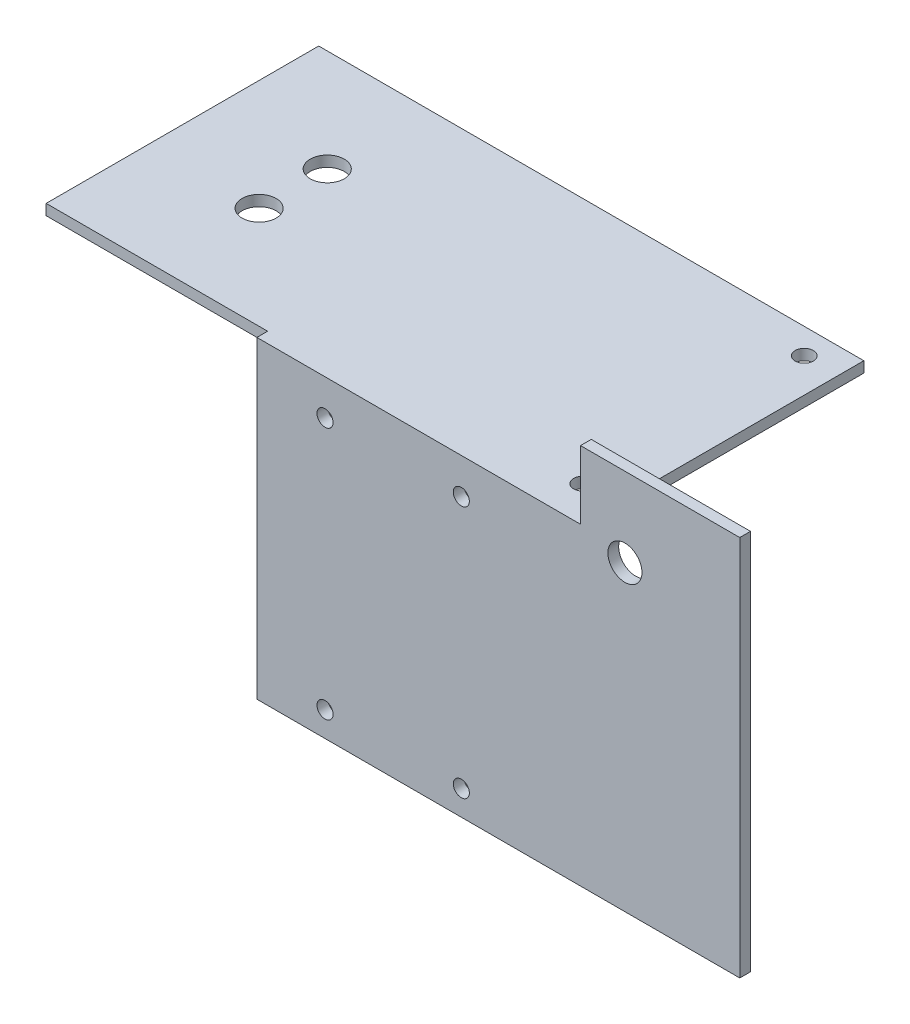
SolidWorks part; units mm, degrees
ref_plane "Front Plane" through (0, 0, 0) normal (0, 0, 1) x (1, 0, 0)
ref_plane "Top Plane" through (0, 0, 0) normal (0, 1, 0) x (1, 0, 0)
ref_plane "Right Plane" through (0, 0, 0) normal (1, 0, 0) x (0, 0, -1)
sketch "Sketch1" plane through (0, 0, 0) normal (0, 0, 1) x (1, 0, 0)
  line L0 (38.1, 51.75) -> (12.7, 51.75) construction
  line L1 (0, 58.4) -> (60.325, 58.4)
  line L2 (0, 58.4) -> (0, 0)
  line L3 (0, 0) -> (90, 0)
  line L4 (60.325, 58.4) -> (60.325, 71.1)
  line L5 (60.325, 71.1) -> (90, 71.1)
  line L6 (12.7, 51.75) -> (12.7, 4.65) construction
  line L7 (90, 71.1) -> (90, 0)
  line L8 (12.7, 4.65) -> (38.1, 4.65) construction
  line L9 (38.1, 51.75) -> (38.1, 4.65) construction
  circle A0 centre (68.6, 56.332) radius 3.175
  circle A4 centre (12.7, 51.75) radius 1.5
  circle A5 centre (38.1, 51.75) radius 1.5
  circle A6 centre (12.7, 4.65) radius 1.5
  circle A7 centre (38.1, 4.65) radius 1.5
  dimension "D3" = 3
  dimension "D10" = 21.4
  dimension "D11" = 6.35
  dimension "D1" = 58.4
  dimension "D2" = 90
  dimension "D4" = 47.1
  dimension "D5" = 60.325
  dimension "D6" = 4.65
  dimension "D7" = 25.4
  dimension "D8" = 12.7
  dimension "D9" = 12.7
  dimension "D12" = 2.068
extrude "Boss-Extrude1" add sketch "Sketch1" against normal blind 2
sketch "Sketch2" plane through (0, 0, -2) normal (0, 0, -1) x (-1, 0, 0)
  line L0 (0, 56.4) -> (41.275, 56.4)
  line L1 (0, 58.4) -> (0, 0) construction
  line L2 (0, 56.4) -> (-60.325, 56.4)
  line L3 (-60.325, 56.4) -> (-60.325, 58.4)
  line L5 (-60.325, 58.4) -> (0, 58.4)
  line L6 (41.275, 56.4) -> (41.275, 58.4)
  line L7 (41.275, 58.4) -> (0, 58.4)
  point P8 (0, 0)
  point P9 (2.8357, 59.6307)
  point P10 (0, 0)
  dimension "D1" = 60.325
  dimension "D2" = 41.275
  dimension "D3" = 2
extrude "Boss-Extrude2" add sketch "Sketch2" along normal blind 50.8
sketch "Sketch3" plane through (0, 58.4, 0) normal (0, 1, 0) x (1, 0, 0)
  line L0 (53.975, 48.0375) -> (53.975, 6.7625) construction
  line L1 (-41.275, 52.8) -> (60.325, 52.8) construction
  line L2 (60.325, 52.8) -> (60.325, 2) construction
  line L3 (-20.6375, 33.75) -> (-20.6375, 21.05) construction
  line L4 (-41.275, 52.8) -> (-41.275, 2) construction
  circle A0 centre (53.975, 48.0375) radius 1.7
  circle A1 centre (53.975, 6.7625) radius 1.7
  circle A2 centre (-20.6375, 33.75) radius 3.175
  circle A3 centre (-20.6375, 21.05) radius 3.175
  point P10 (-20.6375, 27.4)
  point P13 (-41.275, 27.4)
  dimension "D1" = 3.4
  dimension "D2" = 41.275
  dimension "D6" = 6.35
  dimension "D7" = 6.35
  dimension "D3" = 4.7625
  dimension "D4" = 6.35
  dimension "D5" = 12.7
  dimension "D8" = 20.6375
extrude "Cut-Extrude1" cut sketch "Sketch3" against normal through all
